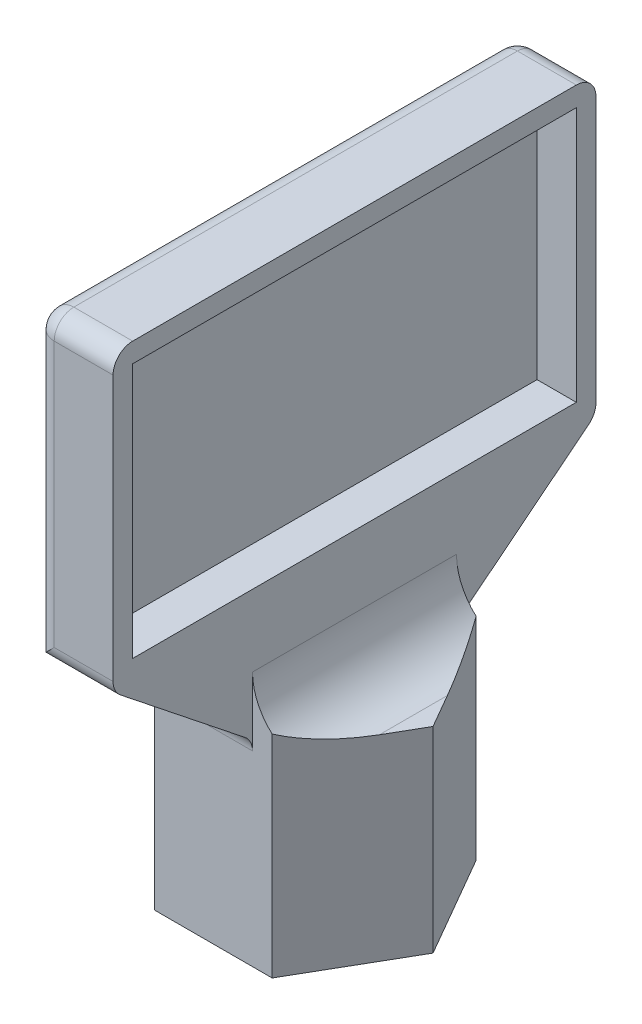
SolidWorks part; units mm, degrees
ref_plane "Front Plane" through (0, 0, 0) normal (0, 0, 1) x (1, 0, 0)
ref_plane "Top Plane" through (0, 0, 0) normal (0, 1, 0) x (1, 0, 0)
ref_plane "Right Plane" through (0, 0, 0) normal (1, 0, 0) x (0, 0, -1)
sketch "Sketch1" plane through (0, 0, 0) normal (0, 1, 0) x (1, 0, 0)
  line L1 (6, 0) -> (3, 5.1962)
  line L2 (3, 5.1962) -> (-3, 5.1962)
  line L3 (-3, 5.1962) -> (-6, 0)
  line L4 (-6, 0) -> (-3, -5.1962)
  line L5 (-3, -5.1962) -> (3, -5.1962)
  line L6 (3, -5.1962) -> (6, 0)
  circle A0 centre (0, 0) radius 5.1962 construction
  dimension "D1" = 6
extrude "Boss-Extrude1" add sketch "Sketch1" along normal blind 10
sketch "Sketch2" plane through (0, 0, 0) normal (0, -1, 0) x (1, 0, 0)
  circle A0 centre (0, 0) radius 3
extrude "Cut-Extrude1" cut sketch "Sketch2" against normal blind 8
sketch "Sketch3" plane through (0, 0, 0) normal (1, 0, 0) x (0, 0, -1)
  line L0 (5.1962, 10) -> (0, 10) construction
  line L1 (0, 10) -> (-5.1962, 10) construction
  line L2 (5.1962, 10) -> (0, 10)
  line L3 (0, 10) -> (-5.1962, 10)
  line L4 (0, 10) -> (0, 43.2722) construction
  line L5 (12.3, 30.6517) -> (-12.3, 30.6517)
  line L6 (-12.3, 30.6517) -> (-12.3, 15.6517)
  line L7 (-12.3, 15.6517) -> (-5.1962, 10)
  line L8 (12.3, 15.6517) -> (5.1962, 10)
  line L9 (12.3, 30.6517) -> (12.3, 15.6517)
  point P11 (0, 30.6517)
  dimension "D1" = 12.3
  dimension "D2" = 15
extrude "Boss-Extrude2" add sketch "Sketch3" along normal blind 2 and the other way blind 2 contours L4 L2 L8 L9 L5 | L3 L4 L5 L6 L7 region at (0, 21.0503, -5.8255) region at (0, 21.0503, 5.8255)
sketch "Sketch4" plane through (2, 0, 0) normal (1, 0, 0) x (0, 0, -1)
  line L6 (-11.3, 29.6517) -> (11.3, 29.6517)
  line L7 (-11.3, 29.6517) -> (-11.3, 16.6517)
  line L8 (-11.3, 16.6517) -> (11.3, 16.6517)
  line L9 (11.3, 29.6517) -> (11.3, 16.6517)
  line L10 (-11.3, 29.6517) -> (11.3, 16.6517) construction
  line L11 (-11.3, 16.6517) -> (11.3, 29.6517) construction
  point P10 (0, 23.1517)
extrude "Cut-Extrude3" cut sketch "Sketch4" against normal blind 2
fillet "Fillet1" radius 1 9 edges at (-2, 23.1517, -12.3) (-2, 30.6517, 0) (-2, 23.1517, 12.3) (0, 10, -5.1962) (0, 10, 5.1962) (0, 15.6517, 12.3) (0, 15.6517, -12.3) (0, 30.6517, -12.3) (0, 30.6517, 12.3)
fillet "Fillet2" radius 3 2 edges at (-2, 10, 0) (2, 10, 0)
